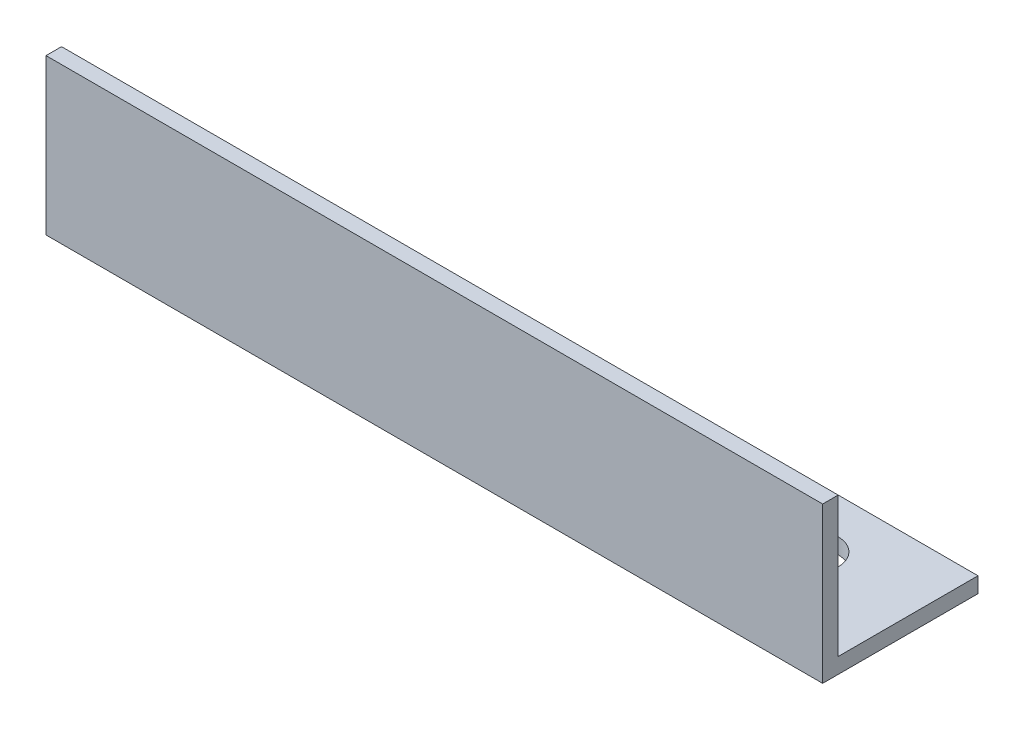
SolidWorks part; units mm, degrees
ref_plane "Спереди" through (0, 0, 0) normal (0, 0, 1) x (1, 0, 0)
ref_plane "Сверху" through (0, 0, 0) normal (0, 1, 0) x (1, 0, 0)
ref_plane "Справа" through (0, 0, 0) normal (1, 0, 0) x (0, 0, -1)
sketch "Эскиз1" plane through (0, 0, 0) normal (1, 0, 0) x (0, 0, -1)
  line L0 (0, 0) -> (0, 30)
  line L1 (0, 0) -> (30, 0)
extrude "Вытянуть-Тонкостенный1" add sketch "Эскиз1" along normal blind 150 thin thin type one direction reverse wall 3
sketch "Эскиз2" plane through (0, 0, 0) normal (0, -1, 0) x (1, 0, 0)
  line L0 (75, -34.5488) -> (75, 3.8648) construction
  circle A0 centre (130, -18) radius 5
  circle A1 centre (100, -18) radius 5
  circle A2 centre (50, -18) radius 5
  circle A3 centre (20, -18) radius 5
  dimension "D1" = 2
extrude "Вырез-Вытянуть1" cut sketch "Эскиз2" against normal through all
